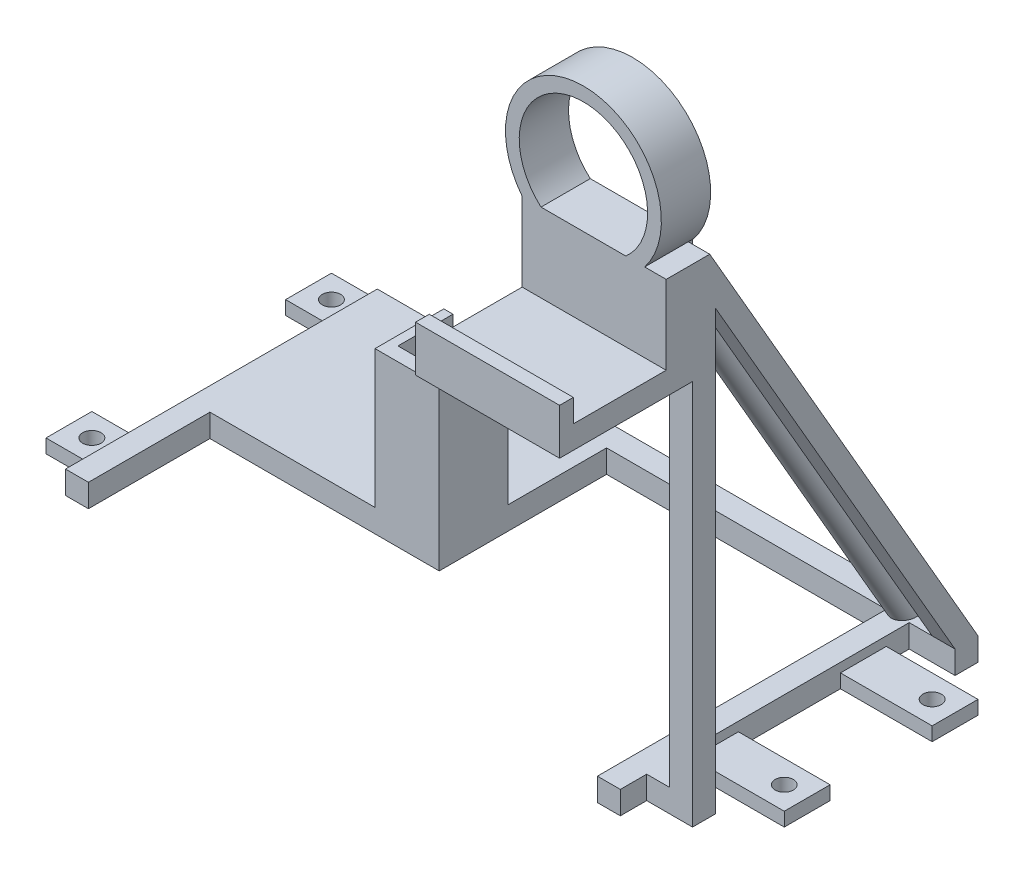
SolidWorks part; units mm, degrees
note: The reader was unsure of these and kept them because the rebuilt part matched: shared geometry of "Sketch23<2>".
ref_plane "Front Plane" through (0, 0, 0) normal (0, 0, 1) x (1, 0, 0)
ref_plane "Top Plane" through (0, 0, 0) normal (0, 1, 0) x (1, 0, 0)
ref_plane "Right Plane" through (0, 0, 0) normal (1, 0, 0) x (0, 0, -1)
sketch "Sketch1" plane through (0, 0, 0) normal (0, 1, 0) x (1, 0, 0)
  line L1 (0, 0) -> (121, 0)
  line L2 (0, 0) -> (0, -68)
  line L3 (0, -68) -> (121, -68)
  line L4 (121, 0) -> (121, -68)
  line L5 (5, -68) -> (116, -68)
  line L6 (5, -68) -> (5, -5)
  line L7 (5, -5) -> (116, -5)
  line L8 (116, -68) -> (116, -5)
  dimension "D1" = 121
  dimension "D2" = 68
  dimension "D3" = 5
  dimension "D4" = 5
  dimension "D5" = 5
extrude "Boss-Extrude1" add sketch "Sketch1" along normal blind 5 contours L8 L3 L4 L1 L2 L6 L7
ref_plane "Plane1" through (0, 3.75, 2.1651) normal (0, 0.866, 0.5) x (1, 0, 0)
sketch "Sketch2" plane through (0, 3.75, 2.1651) normal (0, 0.866, 0.5) x (1, 0, 0)
  line L2 (121, 2.5) -> (121, -56.3897) construction
  line L3 (0, 2.5) -> (121, 2.5) construction
  circle A0 centre (118.2001, -0.2999) radius 2.5
  dimension "D1" = 5
  dimension "D2" = 2.7999
  dimension "D3" = 2.7999
extrude "Boss-Extrude2" add sketch "Sketch2" along normal blind 100
ref_plane "Plane2" through (0, 0, 68) normal (0, 0, 1) x (1, 0, 0)
sketch "Sketch3" plane through (121, 0, 0) normal (1, 0, 0) x (0, 0, -1)
  line L0 (0, 5) -> (-68, 5) construction
  line L1 (0, 0) -> (-5, 0)
  line L2 (0, 0) -> (0, 5)
  line L3 (0, 5) -> (-5, 5)
  line L4 (-5, 0) -> (-5, 5)
  dimension "D1" = 5
extrude "Boss-Extrude3" add sketch "Sketch3" along normal blind 10
sketch "Sketch5" plane through (0, 3.75, 2.1651) normal (0, 0.866, 0.5) x (1, 0, 0)
  line L0 (131, -1.8301) -> (121, -1.8301) construction
  line L1 (131, 2.5) -> (126, 2.5)
  line L2 (131, 2.5) -> (131, -1.8301)
  line L3 (131, -1.8301) -> (126, -1.8301)
  line L4 (126, 2.5) -> (126, -1.8301)
  dimension "D1" = 5
extrude "Boss-Extrude4" add sketch "Sketch5" along normal offset from surface (117 mm away) 17 up to face at (118.2001, 88.9526, 54.5898) offset beyond the face yes
sketch "Sketch6" plane through (0, 1.25, -2.1651) normal (0, 0.5, -0.866) x (-1, 0, 0)
  line L0 (-126, 121.3301) -> (-126, 4.3301) construction
  line L1 (-131, 121.3301) -> (-126, 121.3301)
  line L2 (-131, 121.3301) -> (-131, 116.3301)
  line L3 (-131, 116.3301) -> (-126, 116.3301)
  line L4 (-126, 121.3301) -> (-126, 116.3301)
  dimension "D1" = 5
extrude "Boss-Extrude5" add sketch "Sketch6" along normal blind 20
sketch "Sketch7" plane through (126, 0, 0) normal (-1, 0, 0) x (0, 0, 1)
  line L0 (45.5096, 113.825) -> (41.1795, 116.325)
  line L1 (41.1795, 116.325) -> (62.25, 104.1599) construction
  line L2 (41.1795, 116.325) -> (38.6795, 111.9948)
  line L3 (38.6795, 111.9948) -> (43.0096, 109.4948)
  line L4 (38.6795, 111.9948) -> (56, 101.9948) construction
  line L5 (43.0096, 109.4948) -> (45.5096, 113.825)
  dimension "D1" = 90
  dimension "D2" = 5
extrude "Boss-Extrude6" add sketch "Sketch7" along normal blind 15
sketch "Sketch9" plane through (121, 0, 0) normal (1, 0, 0) x (0, 0, -1)
  line L0 (-62.25, 104.1599) -> (-62.25, 5) construction
  line L1 (-5, 5) -> (-68, 5) construction
  line L2 (-5, 0) -> (-68, 0) construction
  line L3 (-62.25, 5) -> (-57.25, 5)
  line L4 (-62.25, 5) -> (-62.25, 0)
  line L5 (-62.25, 0) -> (-57.25, 0)
  line L6 (-57.25, 5) -> (-57.25, 0)
  dimension "D1" = 5
extrude "Boss-Extrude7" add sketch "Sketch9" along normal up to surface (10 mm away) up to face at (131, 55.5593, 26.0136)
sketch "Sketch10" plane through (0, 5, 0) normal (0, 1, 0) x (1, 0, 0)
  line L0 (131, -57.25) -> (121, -57.25) construction
  line L1 (126, -57.25) -> (131, -57.25)
  line L2 (126, -57.25) -> (126, -62.25)
  line L3 (126, -62.25) -> (131, -62.25)
  line L4 (131, -57.25) -> (131, -62.25)
extrude "Boss-Extrude8" add sketch "Sketch10" along normal up to vertex
sketch "Sketch11" plane through (0, 0, 0) normal (-1, 0, 0) x (0, 0, 1)
  line L1 (62.25, 0) -> (52.25, 0)
  line L2 (62.25, 0) -> (62.25, 3)
  line L3 (62.25, 3) -> (52.25, 3)
  line L4 (52.25, 0) -> (52.25, 3)
  line L5 (0, 0) -> (10, 0)
  line L6 (0, 0) -> (0, 3)
  line L7 (0, 3) -> (10, 3)
  line L8 (10, 0) -> (10, 3)
  dimension "D1" = 10
  dimension "D2" = 3
  dimension "D3" = 10
  dimension "D4" = 3
extrude "Boss-Extrude9" add sketch "Sketch11" along normal blind 10
sketch "Sketch13" plane through (0, 3, 0) normal (0, 1, 0) x (1, 0, 0)
  line L0 (-5, -3) -> (-5, 0) construction
  line L1 (-10, 0) -> (0, 0) construction
  line L2 (-7, -5) -> (-10, -5) construction
  line L3 (-10, -10) -> (-10, 0) construction
  line L4 (-7, -57.25) -> (-10, -57.25) construction
  line L5 (-10, -62.25) -> (-10, -52.25) construction
  circle A0 centre (-5, -5) radius 2
  circle A1 centre (-5, -57.25) radius 2
  dimension "D1" = 4
extrude "Cut-Extrude1" cut sketch "Sketch13" against normal through all both and the other way through all
sketch "Sketch14" plane through (121, 0, 0) normal (1, 0, 0) x (0, 0, -1)
  line L0 (-5, 0) -> (-57.25, 0) construction
  line L1 (-20, 0) -> (-10, 0)
  line L2 (-20, 0) -> (-20, 3)
  line L3 (-20, 3) -> (-10, 3)
  line L4 (-10, 0) -> (-10, 3)
  line L5 (-57.25, 0) -> (-57.25, 5) construction
  line L6 (-42.25, 0) -> (-52.25, 0)
  line L7 (-42.25, 0) -> (-42.25, 3)
  line L8 (-42.25, 3) -> (-52.25, 3)
  line L9 (-52.25, 0) -> (-52.25, 3)
  line L10 (-5, 5) -> (-5, 0) construction
  dimension "D1" = 10
  dimension "D2" = 3
  dimension "D3" = 10
  dimension "D4" = 3
  dimension "D5" = 5
  dimension "D6" = 5
extrude "Boss-Extrude10" add sketch "Sketch14" along normal blind 20
sketch "Sketch15" plane through (0, 3, 0) normal (0, 1, 0) x (1, 0, 0)
  line L0 (138, -15) -> (141, -15) construction
  line L1 (141, -10) -> (141, -20) construction
  line L2 (136, -13) -> (136, -10) construction
  line L3 (141, -10) -> (121, -10) construction
  line L4 (136, -45.25) -> (136, -42.25) construction
  line L5 (141, -42.25) -> (121, -42.25) construction
  line L6 (138, -47.25) -> (141, -47.25) construction
  line L7 (141, -42.25) -> (141, -52.25) construction
  circle A0 centre (136, -15) radius 2
  circle A1 centre (136, -47.25) radius 2
  point P22 (141, -47.25)
  dimension "D1" = 4
extrude "Cut-Extrude2" cut sketch "Sketch15" against normal through all both and the other way through all
sketch "Sketch16" plane through (126, 0, 0) normal (-1, 0, 0) x (0, 0, 1)
  line L0 (49.8397, 111.325) -> (67, 101.4175)
  line L1 (49.8397, 111.325) -> (47.3397, 106.9948)
  line L2 (67, 101.4175) -> (64.5, 97.0874)
  line L3 (47.3397, 106.9948) -> (64.5, 97.0874)
  line L4 (45.5096, 113.825) -> (62.25, 104.1599) construction
  line L5 (43.0096, 109.4948) -> (56, 101.9948) construction
  line L6 (68, -54.223) -> (68, 54.223) construction
  line L7 (43.0096, 109.4948) -> (45.5096, 113.825) construction
  point P13 (44.2596, 111.6599)
  dimension "D1" = 1
  dimension "D2" = 90
  dimension "D3" = 5
extrude "Boss-Extrude11" add sketch "Sketch16" along normal blind 7.8
sketch "Sketch17" plane through (0, 105.075, 60.6651) normal (0, 0.866, 0.5) x (1, 0, 0)
  line L1 (131, 22.5) -> (108.821, 22.5)
  line L2 (131, 22.5) -> (131, 2.5)
  line L3 (131, 2.5) -> (108.821, 2.5)
  line L4 (108.821, 22.5) -> (108.821, 2.5)
  line L5 (0, 2.5) -> (126, 2.5) construction
extrude "Cut-Extrude3" cut sketch "Sketch17" against normal through all both and the other way through all
sketch "Sketch18" plane through (0, 0, 62.25) normal (0, 0, 1) x (1, 0, 0)
  line L0 (126, 104.1599) -> (118.2, 104.1599)
  line L1 (118.2, 104.1599) -> (102.2, 104.1599) construction
  line L2 (102.2, 104.1599) -> (100.7, 104.1599)
  arc A0 (102.2, 104.1599) -> (118.2, 104.1599) centre (110.2, 104.1599) cw
  arc A1 (100.7, 104.1599) -> (119.7, 104.1599) centre (110.2, 104.1599) cw
  dimension "D1" = 7.8
  dimension "D2" = 16
  dimension "D3" = 1.5
extrude "Boss-Extrude12" add sketch "Sketch18" along normal up to surface (5.75 mm away) and the other way blind 5 separate body contours A1 L2 A0 L0 up to plane "Plane2"
sketch "Sketch19" plane through (0, 104.1599, 0) normal (0, -1, 0) x (1, 0, 0)
  line L4 (119.7, 57.25) -> (119.7, 68)
  line L5 (119.7, 68) -> (118.2, 68)
  line L6 (118.2, 68) -> (118.2, 57.25)
  line L7 (118.2, 57.25) -> (119.7, 57.25)
  line L8 (119.7, 57.25) -> (119.7, 68)
  line L9 (119.7, 68) -> (118.2, 68)
  line L10 (118.2, 68) -> (118.2, 57.25)
  line L11 (118.2, 57.25) -> (119.7, 57.25)
  dimension "D1" = 0
extrude "Boss-Extrude13" add sketch "Sketch19" along normal up to vertex (2.7424 mm away) up to point (118.2, 101.4175, 67)
sketch "Sketch20" plane through (0, -3.6575, 6.3349) normal (0, -0.5, 0.866) x (1, 0, 0)
  line L5 (126, 116.3301) -> (126, 121.3301)
  line L6 (126, 121.3301) -> (119.7, 121.3301)
  line L7 (119.7, 121.3301) -> (118.2, 121.3301)
  line L8 (118.2, 121.3301) -> (118.2, 116.3301)
  line L9 (118.2, 116.3301) -> (126, 116.3301)
  line L10 (126, 116.3301) -> (126, 121.3301)
  line L11 (126, 121.3301) -> (119.7, 121.3301)
  line L12 (119.7, 121.3301) -> (118.2, 121.3301)
  line L13 (118.2, 121.3301) -> (118.2, 116.3301)
  line L14 (118.2, 116.3301) -> (126, 116.3301)
  dimension "D1" = 0
sketch "Sketch21" plane through (0, 101.4175, 0) normal (0, -1, 0) x (1, 0, 0)
  line L4 (118.2, 67) -> (119.7, 67)
  line L5 (119.7, 67) -> (119.7, 68)
  line L6 (119.7, 68) -> (118.2, 68)
  line L7 (118.2, 68) -> (118.2, 67)
  line L9 (119.7, 67) -> (119.7, 68)
  line L10 (119.7, 68) -> (118.2, 68)
  line L11 (118.2, 68) -> (118.2, 67)
  line L12 (118.2, 67) -> (119.7, 67)
  dimension "D1" = 0
extrude "Boss-Extrude15" add sketch "Sketch21" along normal blind 1
extrude "Boss-Extrude17" add sketch "Sketch20" against normal up to surface (1.1547 mm away)
ref_plane "Plane3" through (0, 104.1599, 0) normal (0, -1, 0) x (-1, 0, 0)
sketch "Sketch23" plane through (0, 104.1599, 0) normal (0, -1, 0) x (-1, 0, 0)
  line L1 (-126, -56) -> (-118.2, -56)
  line L2 (-126, -56) -> (-126, -68)
  line L3 (-126, -68) -> (-118.2, -68)
  line L4 (-118.2, -56) -> (-118.2, -68)
  dimension "D1" = 7.8
  dimension "D2" = 12
extrude "Cut-Extrude4" cut sketch "Sketch23" along normal blind 10 from offset 2
extrude "Boss-Extrude19" add sketch "Sketch23<2>" along normal blind 5 and the other way up to vertex (2.1651 mm away) other way up to point (119.45, 106.325, 58.5)
sketch "Sketch23<2>" plane through (0, 104.1599, 0) normal (0, -1, 0) x (-1, 0, 0) same geometry as "Sketch23"
sketch "Sketch24" plane through (0, 0, 56) normal (0, 0, -1) x (-1, 0, 0)
  line L5 (-126, 106.325) -> (-126, 101.9948)
  line L6 (-126, 101.9948) -> (-126, 99.1599)
  line L7 (-126, 99.1599) -> (-118.2, 99.1599)
  line L8 (-118.2, 99.1599) -> (-118.2, 106.325)
  line L9 (-118.2, 106.325) -> (-126, 106.325)
  line L10 (-126, 106.325) -> (-126, 101.9948)
  line L11 (-126, 101.9948) -> (-126, 99.1599)
  line L12 (-126, 99.1599) -> (-118.2, 99.1599)
  line L13 (-118.2, 99.1599) -> (-118.2, 106.325)
  line L14 (-118.2, 106.325) -> (-126, 106.325)
  dimension "D1" = 0
extrude "Cut-Extrude5" cut sketch "Sketch24" against normal up to surface (1.25 mm away) up to face at (111.5571, 108.2969, 57.25)
sketch "Sketch25" plane through (0, 105.075, 60.6651) normal (0, 0.866, 0.5) x (1, 0, 0)
  line L4 (126, 2.5) -> (126, -1.8301)
  line L5 (126, -1.8301) -> (131, -1.8301)
  line L6 (131, -1.8301) -> (131, 2.5)
  line L7 (131, 2.5) -> (126, 2.5)
  line L8 (126, 2.5) -> (126, -1.8301)
  line L9 (126, -1.8301) -> (131, -1.8301)
  line L10 (131, -1.8301) -> (131, 2.5)
  line L11 (131, 2.5) -> (126, 2.5)
  dimension "D1" = 0
extrude "Boss-Extrude20" add sketch "Sketch25" along normal up to surface (2.5 mm away) up to face at (123.38, 106.325, 61.8)
sketch "Sketch26" plane through (0, 0, 62.25) normal (0, 0, 1) x (1, 0, 0)
  line L1 (131, 104.1599) -> (126, 104.1599)
  line L2 (131, 104.1599) -> (131, 106.325)
  line L3 (131, 106.325) -> (126, 106.325)
  line L4 (126, 104.1599) -> (126, 106.325)
extrude "Cut-Extrude6" cut sketch "Sketch26" along normal blind 5
sketch "Sketch27" plane through (126, 0, 0) normal (1, 0, 0) x (0, 0, -1)
  line L4 (-62.25, 99.1599) -> (-62.25, 106.325)
  line L5 (-62.25, 106.325) -> (-68, 106.325)
  line L6 (-68, 106.325) -> (-68, 99.1599)
  line L7 (-68, 99.1599) -> (-62.25, 99.1599)
  line L8 (-62.25, 99.1599) -> (-62.25, 106.325)
  line L9 (-62.25, 106.325) -> (-68, 106.325)
  line L10 (-68, 106.325) -> (-68, 99.1599)
  line L11 (-68, 99.1599) -> (-62.25, 99.1599)
  dimension "D1" = 0
extrude "Boss-Extrude21" add sketch "Sketch27" along normal up to surface (5 mm away) up to face at (131, 35.35, 34.1667)
sketch "Sketch29" plane through (0, 0, 0) normal (-1, 0, 0) x (0, 0, 1)
  line L0 (26, 0) -> (26, 35) construction
  line L1 (10, 0) -> (52.25, 0) construction
  line L2 (0, 5) -> (0, 3) construction
  line L3 (0, 5) -> (68, 5) construction
  line L4 (38.5, 5) -> (38.5, 35)
  line L6 (38.5, 35) -> (41.5, 35)
  line L7 (38.5, 35) -> (38.5, 5)
  line L8 (38.5, 5) -> (41.5, 5)
  line L9 (41.5, 35) -> (41.5, 5)
  line M7 (68, 5) -> (0, 5)
  dimension "D1" = 30
  dimension "D2" = 26
  dimension "D3" = 35
  dimension "D4" = 12.5
  dimension "D5" = 12.5
  dimension "D6" = 3
extrude "Boss-Extrude22" add sketch "Sketch29" against normal blind 55 contours L9 L6 L4 M7
sketch "Sketch30" plane through (0, 5, 0) normal (0, -1, 0) x (1, 0, 0)
  line L0 (55, 41.5) -> (5, 41.5) construction
  line L1 (55, 38.5) -> (50, 38.5)
  line L2 (55, 38.5) -> (55, 41.5)
  line L3 (55, 41.5) -> (50, 41.5)
  line L4 (50, 38.5) -> (50, 41.5)
  dimension "D1" = 5
extrude "Boss-Extrude23" add sketch "Sketch30" along normal up to surface (5 mm away) up to face at (136, 0, 17)
sketch "Sketch31" plane through (0, 0, 38.5) normal (0, 0, -1) x (-1, 0, 0)
  line L0 (10, 0) -> (-131, 0) construction
  line L1 (-50, 5) -> (-55, 5)
  line L2 (-50, 5) -> (-50, 0)
  line L3 (-50, 0) -> (-55, 0)
  line L4 (-55, 5) -> (-55, 0)
  line L5 (-55, 0) -> (-55, 35) construction
extrude "Boss-Extrude24" add sketch "Sketch31" along normal up to surface (33.5 mm away) up to face at (60.5, 2.5, 5)
sketch "Sketch32" plane through (0, 0, 38.5) normal (0, 0, -1) x (-1, 0, 0)
  line L0 (-53, 9) -> (-41, 9)
  line L1 (-55, 35) -> (-55, 7)
  line L2 (-53, 35) -> (-57, 35)
  line L3 (-57, 35) -> (-57, 9)
  line L4 (-41, 7) -> (-69, 7)
  line L5 (-67, 35) -> (-67, 16)
  line L6 (-67, 35) -> (-69, 35)
  line L7 (-69, 35) -> (-69, 16)
  line L8 (-67, 16) -> (-69, 16)
  line L10 (-41, 7) -> (-41, 9)
  line L13 (-69, 7) -> (-69, 9)
  line L14 (-57, 9) -> (-69, 9)
  line L16 (-43, 16) -> (-41, 16)
  line L17 (-41, 35) -> (-41, 16)
  line L18 (-43, 35) -> (-41, 35)
  line L19 (-43, 35) -> (-43, 16)
  line L20 (-53, 35) -> (-53, 9)
  line M7 (0, 35) -> (-55, 35)
  line M8 (-55, 35) -> (-55, 5)
  dimension "D2" = 10
  dimension "D3" = 2
  dimension "D4" = 19
extrude "Boss-Extrude25" add sketch "Sketch32" along normal blind 12 contours L20 L4 L10 L0 M7 M8 | L19 L16 L17 M7
sketch "Sketch34" plane through (0, 35, 0) normal (0, 1, 0) x (1, 0, 0)
  line L1 (41, -38.5) -> (0, -38.5)
  line L2 (41, -38.5) -> (41, -41.5)
  line L3 (41, -41.5) -> (0, -41.5)
  line L4 (0, -38.5) -> (0, -41.5)
extrude "Cut-Extrude7" cut sketch "Sketch34" against normal up to surface (30 mm away) up to face at (118.2001, 5, 0.3463)
sketch "Sketch35" plane through (0, 7, 0) normal (0, -1, 0) x (1, 0, 0)
  line L4 (55, 38.5) -> (41, 38.5)
  line L5 (41, 38.5) -> (41, 26.5)
  line L6 (41, 26.5) -> (55, 26.5)
  line L7 (55, 26.5) -> (55, 38.5)
  line L8 (55, 38.5) -> (41, 38.5)
  line L9 (41, 38.5) -> (41, 26.5)
  line L10 (41, 26.5) -> (55, 26.5)
  line L11 (55, 26.5) -> (55, 38.5)
  dimension "D1" = 0
extrude "Boss-Extrude26" add sketch "Sketch35" along normal up to surface (7 mm away) up to face at (136, 0, 17)
sketch "Sketch36" plane through (0, 0, 38.5) normal (0, 0, 1) x (1, 0, 0)
  line L4 (50, 0) -> (50, 5)
  line L5 (50, 5) -> (41, 5)
  line L6 (41, 5) -> (41, 0)
  line L7 (41, 0) -> (50, 0)
  line L8 (50, 0) -> (50, 5)
  line L9 (50, 5) -> (41, 5)
  line L10 (41, 5) -> (41, 0)
  line L11 (41, 0) -> (50, 0)
  dimension "D1" = 0
extrude "Boss-Extrude27" add sketch "Sketch36" along normal up to surface and the other way up to surface up to face at (48.6667, 13.3333, 41.5) other way up to face at (27.5, 2.5, 5)
sketch "Sketch37" plane through (41, 0, 0) normal (-1, 0, 0) x (0, 0, 1)
  line L1 (41.5, 0) -> (0, 0)
  line L2 (41.5, 0) -> (41.5, 5)
  line L3 (41.5, 5) -> (0, 5)
  line L4 (0, 0) -> (0, 5)
extrude "Boss-Extrude28" add sketch "Sketch37" along normal up to surface (41 mm away) contours L2 L1 L4 L3 up to face at (0, 2.2, 38.5)
sketch "Sketch38" plane through (118.2, 0, 0) normal (-1, 0, 0) x (0, 0, 1)
  line L1 (44.0573, 123.2063) -> (78.3089, 123.2063)
  line L2 (44.0573, 123.2063) -> (44.0573, 96.1184)
  line L3 (44.0573, 96.1184) -> (78.3089, 96.1184)
  line L4 (78.3089, 123.2063) -> (78.3089, 96.1184)
extrude "Cut-Extrude8" cut sketch "Sketch38" along normal through all
sketch "Sketch39" plane through (0, 106.325, 0) normal (0, 1, 0) x (1, 0, 0)
  line L1 (86.6562, -42.2101) -> (154.3408, -42.2101)
  line L2 (86.6562, -42.2101) -> (86.6562, -72.2403)
  line L3 (86.6562, -72.2403) -> (154.3408, -72.2403)
  line L4 (154.3408, -42.2101) -> (154.3408, -72.2403)
extrude "Cut-Extrude9" cut sketch "Sketch39" along normal through all
sketch "Sketch42" plane through (0, 0, 68) normal (0, 0, 1) x (1, 0, 0)
  line L4 (131, 106.325) -> (118.2, 106.325)
  line L5 (118.2, 106.325) -> (118.2, 99.1599)
  line L6 (118.2, 99.1599) -> (131, 99.1599)
  line L7 (131, 99.1599) -> (131, 106.325)
  line L8 (131, 106.325) -> (118.2, 106.325)
  line L9 (118.2, 106.325) -> (118.2, 99.1599)
  line L10 (118.2, 99.1599) -> (131, 99.1599)
  line L11 (131, 99.1599) -> (131, 106.325)
  dimension "D1" = 0
sketch "Sketch43" plane through (0, 0, 57.25) normal (0, 0, -1) x (-1, 0, 0)
  line L0 (-120.7001, 90.2026) -> (-120.7001, 106.325) construction
  line L1 (-120.7001, 106.325) -> (-122.2001, 106.325) construction
  line L2 (-122.2001, 106.325) -> (-122.2001, 90.2026) construction
  line L3 (-122.2001, 90.2026) -> (-120.7001, 90.2026) construction
  line L4 (-118.2, 106.325) -> (-126, 106.325) construction
  line L5 (-120.7001, 106.325) -> (-104.7001, 106.325) construction
  line L6 (-104.7001, 106.325) -> (-103.7001, 106.325) construction
  line L7 (-104.7001, 106.325) -> (-104.7001, 90.2026) construction
  line L8 (-104.7001, 90.2026) -> (-103.7001, 90.2026) construction
  line L9 (-103.7001, 90.2026) -> (-103.7001, 106.325) construction
  line L10 (-122.2001, 106.325) -> (-126, 106.325)
  line L11 (-103.7001, 106.325) -> (-99.5874, 106.325)
  line L16 (-126, 106.325) -> (-126.3129, 106.325)
  arc A0 (-122.2001, 106.325) -> (-103.7001, 106.325) centre (-112.9501, 116.8339) cw
  arc A1 (-126.3129, 106.325) -> (-99.5874, 106.325) centre (-112.9501, 116.8339) cw
  arc A2 (-124.1823, 104.0731) -> (-101.718, 104.0731) centre (-112.9501, 116.8339) cw construction
  dimension "D4" = 14
  dimension "D1" = 1.5
  dimension "D2" = 16
  dimension "D3" = 1
  dimension "D5" = 3
sketch "Sketch44" plane through (118.2, 0, 0) normal (-1, 0, 0) x (0, 0, 1)
  line L1 (57.25, 106.325) -> (62.25, 106.325)
  line L2 (57.25, 106.325) -> (57.25, 99.1599)
  line L3 (57.25, 99.1599) -> (62.25, 99.1599)
  line L4 (62.25, 106.325) -> (62.25, 99.1599)
extrude "Boss-Extrude30" add sketch "Sketch44" along normal up to vertex (18.6126 mm away) up to point (99.5874, 106.325, 57.25)
extrude "Boss-Extrude31" add sketch "Sketch43" against normal up to surface (10.75 mm away) up to plane "Plane2"
sketch "Sketch45" plane through (0, 0, 62.25) normal (0, 0, 1) x (1, 0, 0)
  line L5 (118.2, 99.1599) -> (118.2, 106.325)
  line L6 (118.2, 106.325) -> (103.7001, 106.325)
  line L7 (103.7001, 106.325) -> (99.5874, 106.325)
  line L8 (99.5874, 106.325) -> (99.5874, 99.1599)
  line L9 (99.5874, 99.1599) -> (118.2, 99.1599)
  line L10 (118.2, 99.1599) -> (118.2, 106.325)
  line L11 (118.2, 106.325) -> (103.7001, 106.325)
  line L12 (103.7001, 106.325) -> (99.5874, 106.325)
  line L13 (99.5874, 106.325) -> (99.5874, 99.1599)
  line L14 (99.5874, 99.1599) -> (118.2, 99.1599)
  dimension "D1" = 0
extrude "Boss-Extrude32" add sketch "Sketch45" along normal up to surface (5.75 mm away) up to face at (118.7751, 111.0359, 68)
sketch "Sketch46" plane through (0, 0, 62.25) normal (0, 0, 1) x (1, 0, 0)
  line L0 (126, 99.1599) -> (126, 5) construction
  line L1 (126, 89.1599) -> (131, 89.1599)
  line L2 (126, 89.1599) -> (126, 84.1599)
  line L3 (126, 84.1599) -> (131, 84.1599)
  line L4 (131, 89.1599) -> (131, 84.1599)
  line L5 (131, 99.1599) -> (131, 0) construction
  line L6 (118.2, 99.1599) -> (131, 99.1599) construction
  dimension "D1" = 5
  dimension "D2" = 10
extrude "EDIT THIS LENGTH" add sketch "Sketch46" along normal blind 29
sketch "Sketch47" plane through (0, 89.1599, 0) normal (0, 1, 0) x (1, 0, 0)
  line L0 (126, -91.25) -> (126, -62.25) construction
  line L1 (126, -88.25) -> (131, -88.25)
  line L2 (126, -88.25) -> (126, -91.25)
  line L3 (126, -91.25) -> (131, -91.25)
  line L4 (131, -88.25) -> (131, -91.25)
  dimension "D1" = 3
extrude "Boss-Extrude34" add sketch "Sketch47" along normal blind 5
sketch "Sketch48" plane through (0, 99.1599, 0) normal (0, -1, 0) x (1, 0, 0)
  line L0 (131, 62.25) -> (126, 62.25) construction
  line L1 (126, 62.75) -> (99.5874, 62.75)
  line L2 (126, 62.75) -> (126, 68)
  line L3 (126, 68) -> (99.5874, 68)
  line L4 (99.5874, 62.75) -> (99.5874, 68)
  line L7 (126, 57.25) -> (126, 62.25) construction
  dimension "D1" = 0.5
extrude "Boss-Extrude35" add sketch "Sketch48" along normal up to surface (15 mm away) up to face at (128.5, 84.1599, 76.75)
sketch "Sketch50" plane through (0, 99.1599, 0) normal (0, -1, 0) x (1, 0, 0)
  line L1 (126, 62.25) -> (131, 62.25)
  line L2 (126, 62.25) -> (126, 68)
  line L3 (126, 68) -> (131, 68)
  line L4 (131, 62.25) -> (131, 68)
extrude "Boss-Extrude36" add sketch "Sketch50" along normal up to surface (10 mm away) up to face at (127.6667, 89.1599, 71.9583)
sketch "Sketch51" plane through (126, 0, 0) normal (-1, 0, 0) x (0, 0, 1)
  line L6 (68, 89.1599) -> (68, 84.1599)
  line L7 (68, 84.1599) -> (91.25, 84.1599)
  line L8 (91.25, 84.1599) -> (91.25, 94.1599)
  line L9 (91.25, 94.1599) -> (88.25, 94.1599)
  line L10 (88.25, 94.1599) -> (88.25, 89.1599)
  line L11 (88.25, 89.1599) -> (68, 89.1599)
  line L12 (68, 89.1599) -> (68, 84.1599)
  line L13 (68, 84.1599) -> (91.25, 84.1599)
  line L14 (91.25, 84.1599) -> (91.25, 94.1599)
  line L15 (91.25, 94.1599) -> (88.25, 94.1599)
  line L16 (88.25, 94.1599) -> (88.25, 89.1599)
  line L17 (88.25, 89.1599) -> (68, 89.1599)
  dimension "D1" = 0
extrude "Boss-Extrude37" add sketch "Sketch51" along normal up to surface (26.4126 mm away) up to face at (99.5874, 96.5483, 62.6667)
chamfer "Chamfer1" distance 16 angle 5 1 edges at (99.5874, 99.1599, 60) first distance on face at (112.7937, 99.1599, 60)
